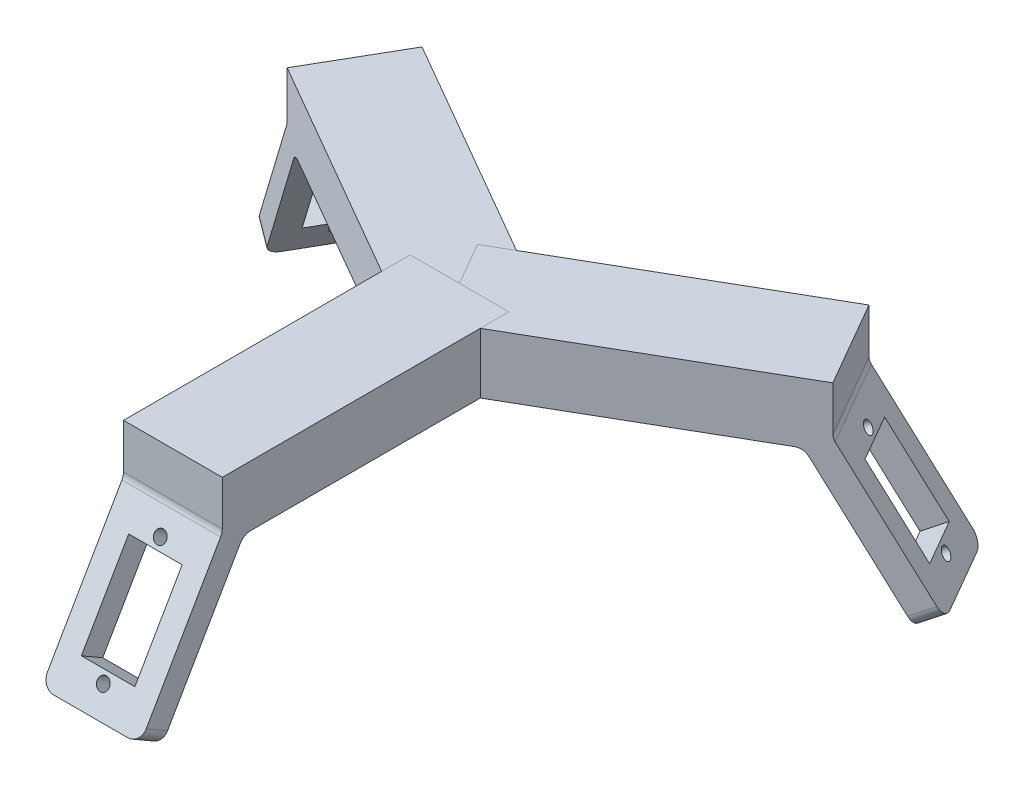
SolidWorks part; units mm, degrees
note: '?' marks a value the reader was unsure of.
ref_plane "前视基准面" through (0, 0, 0) normal (0, 0, 1) x (1, 0, 0)
ref_plane "上视基准面" through (0, 0, 0) normal (0, 1, 0) x (1, 0, 0)
ref_plane "右视基准面" through (0, 0, 0) normal (1, 0, 0) x (0, 0, -1)
ref_axis "基准轴1" through (73.7735, 0, 0) along (-1, 0, 0)?
ref_plane "基准面2" through (0, 0, 0) normal (0, 0.5, 0.866) x (-1, 0, 0)
ref_axis "基准轴2" through (0, 0, 97.5114) along (0, 0, -1)?
ref_plane "基准面3" through (0, 43, 74.4782) normal (0, 0.5, 0.866) x (-1, 0, 0)
sketch "草图4" plane through (0, 43, 74.4782) normal (0, 0.5, 0.866) x (-1, 0, 0)
  line L1 (-6.5, -11.5) -> (6.5, -11.5)
  line L2 (-6.5, -11.5) -> (-6.5, 11.5)
  line L3 (-6.5, 11.5) -> (6.5, 11.5)
  line L4 (6.5, -11.5) -> (6.5, 11.5)
  line L5 (-6.5, -11.5) -> (6.5, 11.5) construction
  line L6 (-6.5, 11.5) -> (6.5, -11.5) construction
  line L7 (-12, -20) -> (12, -20)
  line L8 (-12, -20) -> (-12, 20)
  line L9 (-12, 20) -> (12, 20)
  line L10 (12, -20) -> (12, 20)
  line L11 (-12, -20) -> (12, 20) construction
  line L12 (-12, 20) -> (12, -20) construction
  point P0 (0, 0)
  point P6 (0, 0)
  dimension "D1" = 13
  dimension "D2" = 23
  dimension "D3" = 40
  dimension "D4" = 24
extrude "凸台-拉伸1" add sketch "草图4" along normal blind 6 separate body
ref_axis "基准轴3" through (0, 66.5515, 0) along (0, -1, 0)?
ref_plane "基准面4" through (0, 75, 0) normal (0, 1, 0) x (1, 0, 0)
sketch "草图5" plane through (0, 75, 0) normal (0, 1, 0) x (1, 0, 0)
  line L4 (12, -64.4782) -> (-12, -64.4782)
  line L5 (-12, -64.4782) -> (-12, -69.6743)
  line L6 (-12, -69.6743) -> (12, -69.6743)
  line L7 (12, -69.6743) -> (12, -64.4782)
  line L8 (12, -64.4782) -> (-12, -64.4782)
  line L9 (-12, -64.4782) -> (-12, -69.6743)
  line L10 (-12, -69.6743) -> (12, -69.6743)
  line L11 (12, -69.6743) -> (12, -64.4782)
  dimension "D1" = 0
extrude "凸台-拉伸2" add sketch "草图5" against normal up to next
sketch "草图6" plane through (0, 0, 64.4782) normal (0, 0, -1) x (-1, 0, 0)
  line L4 (-12, 75) -> (-12, 60.3205)
  line L5 (-12, 60.3205) -> (12, 60.3205)
  line L6 (12, 60.3205) -> (12, 75)
  line L7 (12, 75) -> (-12, 75)
  line L8 (-12, 75) -> (-12, 60.3205)
  line L9 (-12, 60.3205) -> (12, 60.3205)
  line L10 (12, 60.3205) -> (12, 75)
  line L11 (12, 75) -> (-12, 75)
  dimension "D1" = 0
extrude "凸台-拉伸3" add sketch "草图6" along normal up to vertex (64.4782 mm away) up to point (0, 0, 0)
pattern_circular "阵列(圆周)13" count 3 over 360 about axis through (0, 0, 0) along (0, 1, 0) of bodies 110
sketch "草图7" plane through (0, 43, 74.4782) normal (0, 0.5, 0.866) x (-1, 0, 0)
  line L0 (0, 48.7557) -> (0, -37.4519) construction
  line L1 (-73.7735, 0) -> (73.7735, 0) construction
  line L2 (0, 0) -> (14.5173, 0) construction
  circle A0 centre (0, 13.85) radius 1.5
  circle A1 centre (0, -13.85) radius 1.5
  dimension "D1" = 13.85
extrude "切除-拉伸1" cut sketch "草图7" along normal blind 10
sketch "草图8" plane through (-64.5, 43, -37.2391) normal (0.75, -0.5, 0.433) x (0.3603, -0.2402, -0.9014)
  line L0 (-15.9851, 55.3742) -> (1.0881, -3.7692) construction
  line L1 (0, 0) -> (6.245, 1.8028)
  line L2 (3.0555, 12.8516) -> (9.4345, -9.2461) construction
  circle A0 centre (-3.8413, 13.3066) radius 1.5
  circle A1 centre (3.8413, -13.3066) radius 1.5
  dimension "D1" = 13.85
extrude "切除-拉伸2" cut sketch "草图8" against normal blind 10 contours A0 | A1
sketch "草图9" plane through (64.5, 43, -37.2391) normal (-0.75, -0.5, 0.433) x (0.3603, 0.2402, 0.9014)
  line L0 (15.9851, 55.3742) -> (-1.0881, -3.7692) construction
  line L1 (0, 0) -> (-6.245, 1.8028) construction
  line L2 (-9.4345, -9.2461) -> (-3.0555, 12.8516) construction
  circle A0 centre (3.8413, 13.3066) radius 1.5
  circle A1 centre (-3.8413, -13.3066) radius 1.5
  dimension "D1" = 13.85
extrude "切除-拉伸3" cut sketch "草图9" against normal blind 10
fillet "圆角1" radius 3 2 edges at (60.3397, 63.3205, -34.8372) (55.8397, 60.3205, -32.2391)
fillet "圆角2" radius 3 2 edges at (0, 63.3205, 69.6743) (0, 60.3205, 64.4782)
fillet "圆角3" radius 3 2 edges at (-60.3397, 63.3205, -34.8372) (-55.8397, 60.3205, -32.2391)
fillet "圆角4" radius 3 2 edges at (69.4103, 27.1795, -53.9304) (81.4103, 27.1795, -33.1458)
fillet "圆角5" radius 3 2 edges at (-81.4103, 27.1795, -33.1458) (-69.4103, 27.1795, -53.9304)
fillet "圆角6" radius 3 2 edges at (-12, 27.1795, 87.0763) (12, 27.1795, 87.0763)
